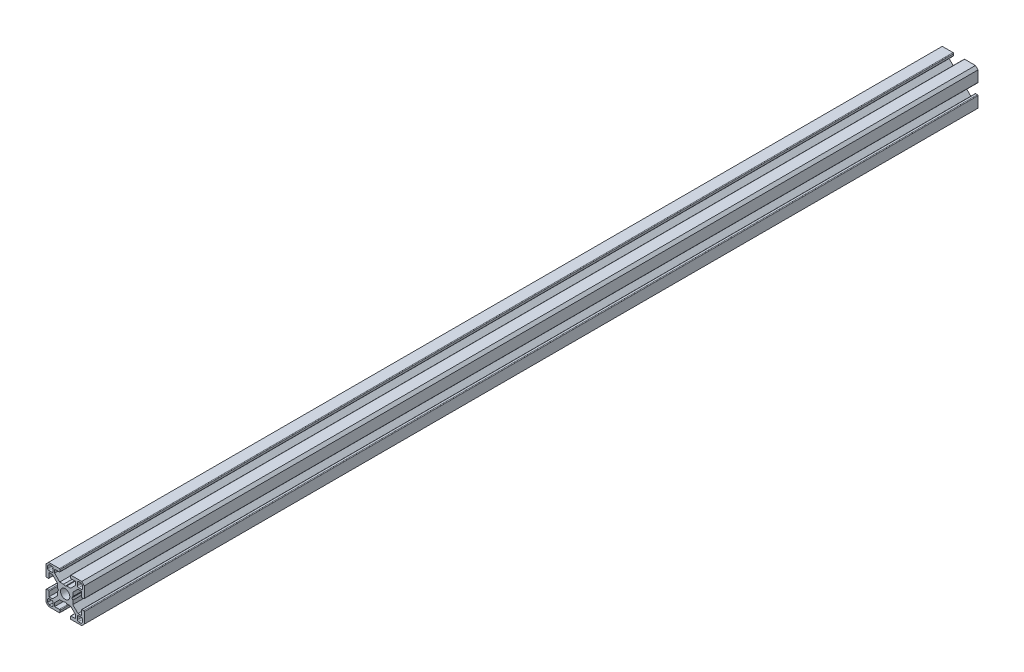
SolidWorks part; units mm, degrees
ref_plane "Front Plane" through (0, 0, 0) normal (0, 0, 1) x (1, 0, 0)
ref_plane "Top Plane" through (0, 0, 0) normal (0, 1, 0) x (1, 0, 0)
ref_plane "Right Plane" through (0, 0, 0) normal (1, 0, 0) x (0, 0, -1)
sketch "Sketch1" plane through (0, 0, 0) normal (0, 0, 1) x (0, -1, 0)
  line L0 (0, 5.3) -> (0, 3.65)
  line L1 (-3.65, 0) -> (-5.3, 0)
  line L24 (0, 5.3) -> (-1.25, 6)
  line L25 (-1.25, 6) -> (-4.2322, 6)
  line L26 (-4.2322, 6) -> (-8.25, 10.0178)
  line L27 (-8.25, 10.0178) -> (-8.25, 12.68)
  line L28 (-8.25, 12.68) -> (-4.55, 12.68)
  line L29 (-4.05, 13.18) -> (-4.05, 14.5)
  line L30 (-4.55, 15) -> (-13, 15)
  line L31 (-13, 15) -> (-15, 13)
  line L32 (-15, 13) -> (-15, 4.55)
  line L33 (-14.5, 4.05) -> (-13.18, 4.05)
  line L34 (-12.68, 4.55) -> (-12.68, 8.25)
  line L35 (-12.68, 8.25) -> (-10.0178, 8.25)
  line L36 (-10.0178, 8.25) -> (-6, 4.2322)
  line L37 (-6, 4.2322) -> (-6, 1.25)
  line L38 (-6, 1.25) -> (-5.3, 0)
  line L60 (-10.5, 9.5) -> (-12.7, 9.5)
  line L61 (-13.7, 10.5) -> (-13.7, 12.4615)
  line L62 (-13.7, 12.4615) -> (-12.4615, 13.7)
  line L63 (-12.4615, 13.7) -> (-10.5, 13.7)
  line L64 (-9.5, 12.7) -> (-9.5, 10.5)
  line L80 (0, 0) -> (0, 15) construction
  line L81 (0, 0) -> (-15.3155, 0) construction
  arc A6 (-4.55, 12.68) -> (-4.05, 13.18) centre (-4.55, 13.18) ccw
  arc A7 (-4.05, 14.5) -> (-4.55, 15) centre (-4.55, 14.5) ccw
  arc A8 (-15, 4.55) -> (-14.5, 4.05) centre (-14.5, 4.55) ccw
  arc A9 (-13.18, 4.05) -> (-12.68, 4.55) centre (-13.18, 4.55) ccw
  arc A16 (-3.65, 0) -> (0, 3.65) centre (0, 0) cw
  arc A17 (-12.7, 9.5) -> (-13.7, 10.5) centre (-12.7, 10.5) cw
  arc A18 (-10.5, 13.7) -> (-9.5, 12.7) centre (-10.5, 12.7) cw
  arc A19 (-9.5, 10.5) -> (-10.5, 9.5) centre (-10.5, 10.5) cw
  dimension "D7" = 1
  dimension "D10" = 3.65
  dimension "D15" = 0.5
  dimension "D1" = 8.4644
  dimension "D2" = 16.5
  dimension "D3" = 8.1
  dimension "D4" = 30
  dimension "D5" = 30
  dimension "D6" = 4.2
  dimension "D8" = 1.3
  dimension "D9" = 1.3
  dimension "D11" = 12
  dimension "D12" = 2.32
  dimension "D13" = 9
  dimension "D14" = 2
  dimension "D16" = 2
  dimension "D17" = 4.2
  dimension "D18" = 1.3
  dimension "D19" = 2.32
  dimension "D20" = 2.5
  dimension "D21" = 0.7
extrude "Boss-Extrude1" add sketch "Sketch1" against normal mid plane 700
ref_axis "EXTRUDE" through (0, 0, 330) along (0, 0, -1)
pattern_circular "CirPattern1" count 4 over 360 about axis through (0, 0, 330) along (0, 0, -1) of "Boss-Extrude1"
equation "\"length\"=70"
equation "\"D1@Boss-Extrude1\"=\"length\""
equation "\"D9@Sketch1\"=\"D8@Sketch1\""
equation "\"D16@Sketch1\"=\"D14@Sketch1\""
equation "\"D17@Sketch1\"=\"D6@Sketch1\""
equation "\"D18@Sketch1\"=\"D8@Sketch1\""
equation "\"D19@Sketch1\"=\"D12@Sketch1\""
